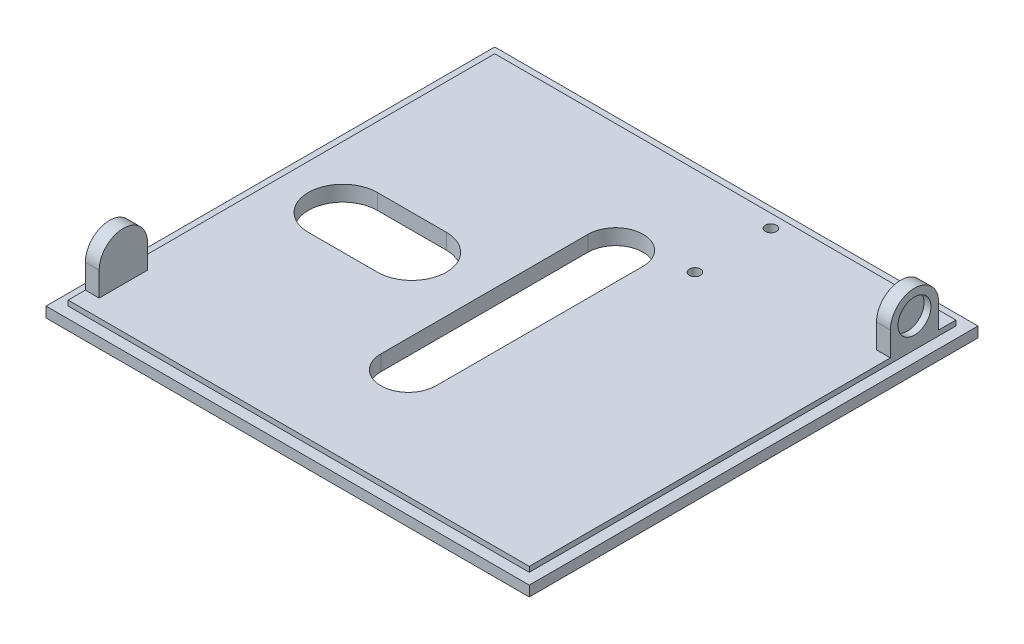
SolidWorks part; units mm, degrees
ref_plane "Front Plane" through (0, 0, 0) normal (0, 0, 1) x (1, 0, 0)
ref_plane "Top Plane" through (0, 0, 0) normal (0, 1, 0) x (1, 0, 0)
ref_plane "Right Plane" through (0, 0, 0) normal (1, 0, 0) x (0, 0, -1)
sketch "Sketch1" plane through (0, 0, 0) normal (0, 1, 0) x (1, 0, 0)
  line L1 (-70, 65) -> (70, 65)
  line L2 (-70, 65) -> (-70, -65)
  line L3 (-70, -65) -> (70, -65)
  line L4 (70, 65) -> (70, -65)
  line L5 (-70, 65) -> (70, -65) construction
  line L6 (-70, -65) -> (70, 65) construction
  point P0 (0, 0)
  dimension "D1" = 140
  dimension "D2" = 130
extrude "Boss-Extrude1" add sketch "Sketch1" along normal blind 3
sketch "Sketch2" plane through (0, 3, 0) normal (0, 1, 0) x (1, 0, 0)
  line L24 (66.8, -61.8) -> (66.8, 61.8)
  line L25 (-66.8, -61.8) -> (66.8, -61.8)
  line L26 (-66.8, 61.8) -> (-66.8, -61.8)
  line L27 (66.8, 61.8) -> (-66.8, 61.8)
  line L28 (66.8, -61.8) -> (66.8, 61.8)
  line L29 (-66.8, -61.8) -> (66.8, -61.8)
  line L30 (-66.8, 61.8) -> (-66.8, -61.8)
  line L31 (66.8, 61.8) -> (-66.8, 61.8)
  dimension "D1" = 3.2
extrude "Boss-Extrude2" add sketch "Sketch2" along normal blind 1.5
sketch "Sketch5" plane through (0, 4.5, 0) normal (0, 1, 0) x (1, 0, 0)
  line L0 (-66.8, 61.8) -> (-66.8, -61.8) construction
  line L1 (-66.8, -42.8) -> (-62.8, -42.8)
  line L2 (-66.8, -42.8) -> (-66.8, -56.8)
  line L3 (-66.8, -56.8) -> (-62.8, -56.8)
  line L4 (-62.8, -42.8) -> (-62.8, -56.8)
  line L5 (-66.8, 61.8) -> (-66.8, -61.8) construction
  line L6 (-66.8, -61.8) -> (66.8, -61.8) construction
  dimension "D1" = 4
  dimension "D2" = 14
  dimension "D3" = 5
extrude "Boss-Extrude3" add sketch "Sketch5" along normal blind 14
sketch "Sketch6" plane through (-66.8, 0, 0) normal (-1, 0, 0) x (0, 0, 1)
  line L0 (56.8, 18.5) -> (56.8, 4.5) construction
  line L1 (42.8, 18.5) -> (56.8, 18.5) construction
  circle A0 centre (49.8, 11.5) radius 4.775
  dimension "D1" = 9.55
  dimension "D2" = 7
  dimension "D3" = 7
extrude "Cut-Extrude3" cut sketch "Sketch6" against normal blind 2
fillet "Fillet1" 2 edges at (-64.8, 18.5, 56.8) (-64.8, 18.5, 42.8) type full round first side face at (-64.8, 11.5, 56.8) second side face at (-64.8, 11.5, 42.8) middle face at (-64.8, 18.5, 49.8)
ref_axis "Axis1" through (0, 19.425, 0) along (0, -1, 0)
pattern_circular "CirPattern2" count 2 every 180 about axis through (0, 19.425, 0) along (0, -1, 0) of "Boss-Extrude3", "Cut-Extrude3", "Fillet1"
sketch "Sketch7" plane through (0, 4.5, 0) normal (0, 1, 0) x (1, 0, 0)
  line L0 (0, -30) -> (0, 30) construction
  line L1 (-8, -30) -> (-8, 30)
  line L2 (8, -30) -> (8, 30)
  arc A0 (-8, -30) -> (8, -30) centre (0, -30) ccw
  arc A1 (8, 30) -> (-8, 30) centre (0, 30) ccw
  point P2 (0, 0)
  dimension "D2" = 8
  dimension "D1" = 60
extrude "Cut-Extrude4" cut sketch "Sketch7" against normal through all
sketch "Sketch8" plane through (0, 0, 0) normal (0, -1, 0) x (1, 0, 0)
  line L0 (-49, 0) -> (-29, 0) construction
  line L1 (-49, 10) -> (-29, 10)
  line L2 (-49, -10) -> (-29, -10)
  arc A0 (-49, 10) -> (-49, -10) centre (-49, 0) ccw
  arc A1 (-29, -10) -> (-29, 10) centre (-29, 0) ccw
  point P3 (-39, 0)
  point P8 (0, 0)
  dimension "D1" = 20
  dimension "D2" = 39
  dimension "D3" = 20
extrude "Cut-Extrude5" cut sketch "Sketch8" against normal through all contours L1 A1 L2 A0
sketch "Sketch9" plane through (0, 0, 0) normal (0, -1, 0) x (1, 0, 0)
  line L2 (70, 65) -> (70, -65) construction
  line L3 (70, -65) -> (-70, -65) construction
  circle A0 centre (17, -36) radius 1.6
  circle A1 centre (17, -58) radius 1.6
  point P4 (0, 0)
  point P5 (15.0641, -28.8705)
  point P6 (16.8629, -45.8513)
  point P7 (17, -27.2371)
  point P8 (0, 0)
  dimension "D1" = 3.2
  dimension "D3" = 53
  dimension "D4" = 29
  dimension "D2" = 22
extrude "Cut-Extrude6" cut sketch "Sketch9" against normal through all
